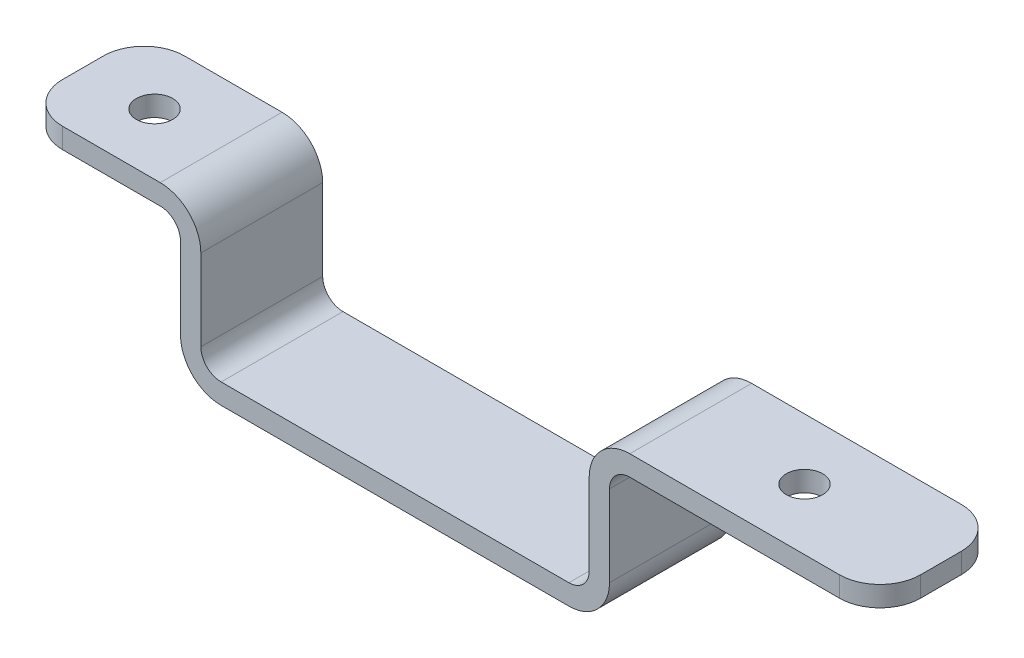
SolidWorks part; units mm, degrees
ref_plane "Front Plane" through (0, 0, 0) normal (0, 0, 1) x (1, 0, 0)
ref_plane "Top Plane" through (0, 0, 0) normal (0, 1, 0) x (1, 0, 0)
ref_plane "Right Plane" through (0, 0, 0) normal (1, 0, 0) x (0, 0, -1)
sketch "Sketch1" plane through (0, 0, 0) normal (0, 0, 1) x (1, 0, 0)
  line L0 (-29.1465, 11.1125) -> (-16.764, 11.1125)
  line L1 (-16.764, 11.1125) -> (-16.764, 0)
  line L2 (-16.764, 0) -> (16.764, 0)
  line L3 (16.764, 0) -> (16.764, 11.1125)
  line L4 (16.764, 11.1125) -> (37.9095, 11.1125)
  line L5 (-29.1465, 11.1125) -> (-29.1465, 12.7)
  line L6 (-29.1465, 12.7) -> (-15.1765, 12.7)
  line L7 (-15.1765, 12.7) -> (-15.1765, 1.5875)
  line L8 (-15.1765, 1.5875) -> (15.1765, 1.5875)
  line L9 (15.1765, 1.5875) -> (15.1765, 12.7)
  line L10 (15.1765, 12.7) -> (37.9095, 12.7)
  line L11 (37.9095, 12.7) -> (37.9095, 11.1125)
  line L13 (0, 0) -> (0, 1.5875) construction
  dimension "D1" = 67.056
  dimension "D2" = 13.97
  dimension "D3" = 33.528
  dimension "D4" = 12.7
  dimension "D5" = 1.5875
  dimension "D6" = 1.5875
  dimension "D7" = 1.5875
  dimension "D8" = 1.5875
extrude "Boss-Extrude1" add sketch "Sketch1" along normal mid plane 9.525
fillet "Fillet1" radius 1.5875 4 edges at (-16.764, 11.1125, 0) (16.764, 11.1125, 0) (15.1765, 1.5875, 0) (-15.1765, 1.5875, 0)
fillet "Fillet2" radius 3.175 4 edges at (-16.764, 0, 0) (16.764, 0, 0) (15.1765, 12.7, 0) (-15.1765, 12.7, 0)
fillet "Fillet3" radius 3.175 4 edges at (37.9095, 11.9062, -4.7625) (37.9095, 11.9062, 4.7625) (-29.1465, 11.9062, -4.7625) (-29.1465, 11.9062, 4.7625)
hole_wizard "Hole1" positions "Sketch3" profile "Sketch2" legacy end condition through all
sketch "Sketch3" plane through (0, 11.1125, 0) normal (0, -1, 0) x (1, 0, 0)
  line L6 (37.9095, 1.5875) -> (37.9095, -1.5875) construction
  line L7 (37.9095, 0) -> (18.3515, 0) construction
  line L8 (18.3515, 4.7625) -> (18.3515, -4.7625) construction
  point P0 (27.2415, 0)
  dimension "D1" = 10.668
sketch "Sketch2" plane through (27.2415, 11.1125, 0) normal (1, 0, 0) x (0, 0, -1)
  line L0 (0, 0) -> (0, 1.5875)
  line L1 (0, 1.5875) -> (1.4224, 1.5875)
  line L2 (1.4224, 1.5875) -> (1.4224, 0)
  line L3 (1.4224, 0) -> (0, 0)
  line L4 (0, 110) -> (0, -10) construction
  dimension "Diameter" = 2.8448
  dimension "Depth" = 1.5875
hole_wizard "Hole2" positions "Sketch5" profile "Sketch4" legacy end condition through all
sketch "Sketch5" plane through (0, 11.1125, 0) normal (0, -1, 0) x (1, 0, 0)
  line L1 (-29.1465, 1.5875) -> (-29.1465, -1.5875) construction
  line L2 (-18.3515, -4.7625) -> (-18.3515, 4.7625) construction
  line L4 (-29.1465, 0) -> (-18.3515, 0) construction
  point P0 (-23.5585, 0)
  dimension "D1" = 5.588
sketch "Sketch4" plane through (-23.5585, 11.1125, 0) normal (1, 0, 0) x (0, 0, -1)
  line L0 (0, 0) -> (0, 1.5875)
  line L1 (0, 1.5875) -> (1.4224, 1.5875)
  line L2 (1.4224, 1.5875) -> (1.4224, 0)
  line L3 (1.4224, 0) -> (0, 0)
  line L4 (0, 110) -> (0, -10) construction
  dimension "Diameter" = 2.8448
  dimension "Depth" = 1.5875
ref_point "Point1"
ref_point "Point2"
